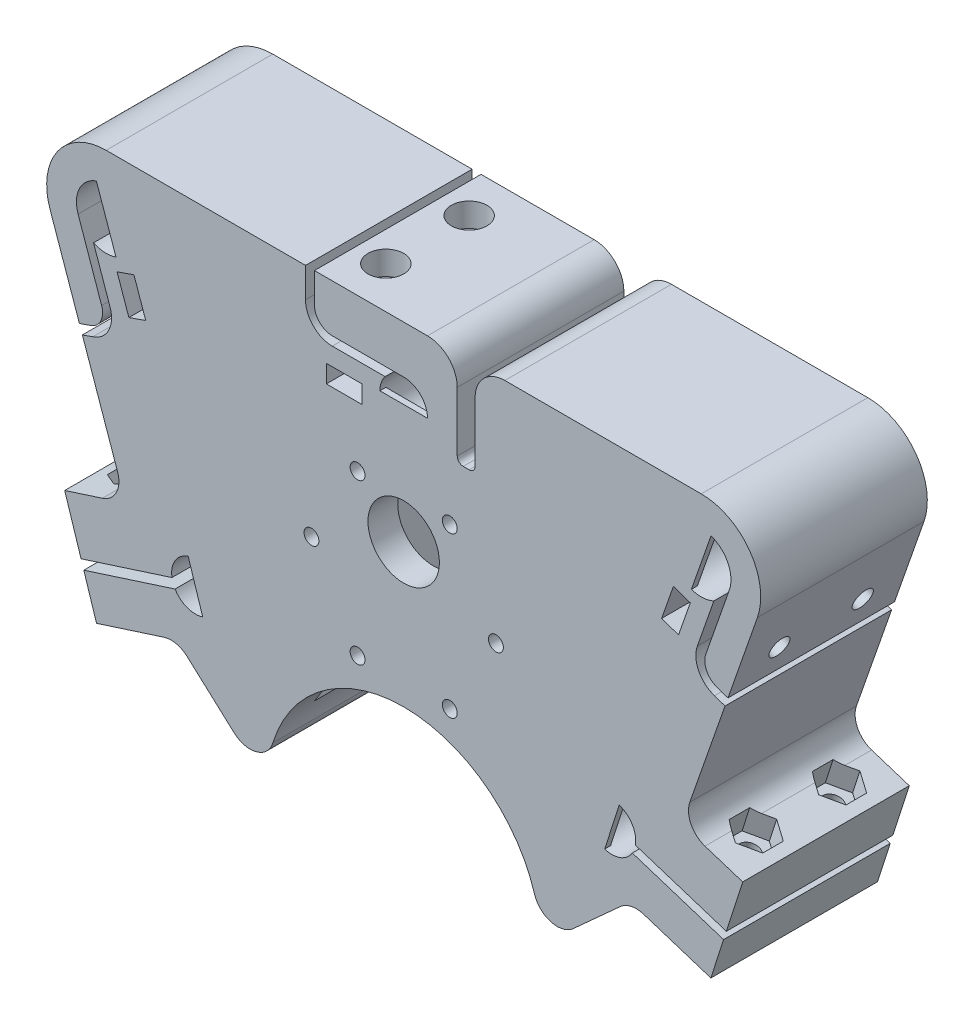
SolidWorks part; units mm, degrees
other "Uwaga1"
sketch "Szkic11" plane through (60, 10, 0) normal (0.4049, 0.0419, -0.9134) x (0.8662, -0.3375, 0.3685)
other "Uwaga2"
sketch "Szkic12" plane through (60, 10, 0) normal (0.4049, 0.0419, -0.9134) x (0.8662, -0.3375, 0.3685)
other "Uwaga3"
sketch "Szkic13"
ref_plane "Płaszczyzna przednia" through (0, 0, 0) normal (0, 0, 1) x (1, 0, 0)
ref_plane "Płaszczyzna górna" through (0, 0, 0) normal (0, 1, 0) x (1, 0, 0)
ref_plane "Płaszczyzna prawa" through (0, 0, 0) normal (1, 0, 0) x (0, 0, -1)
sketch "Szkic1" plane through (0, 0, 0) normal (0, 0, 1) x (1, 0, 0)
  line L0 (-50, 10) -> (4, 10)
  line L1 (-59.4412, -3.296) -> (-43.4971, -48.9664)
  line L2 (43.4971, -48.9664) -> (59.4412, -3.296)
  line L3 (-41.0394, -52.6727) -> (-23, -69)
  line L4 (23, -69) -> (41.0394, -52.6727)
  line L5 (38.4257, -48.0651) -> (43.2433, -49.6122)
  line L6 (38.9457, -46.6566) -> (43.7633, -48.2037)
  line L7 (0, -34.7604) -> (35, -46) construction
  line L8 (38.1168, -55.318) -> (51.621, -59.6546)
  line L9 (51.621, -59.6546) -> (53.7613, -52.9898)
  line L10 (53.7613, -52.9898) -> (43.2433, -49.6122)
  line L11 (43.7633, -48.2037) -> (54.2199, -51.5616)
  line L12 (54.2199, -51.5616) -> (56.9717, -42.9926)
  line L13 (56.9717, -42.9926) -> (46.7307, -39.704)
  line L14 (0, -29) -> (0, -114.3862) construction
  line L15 (0, 2) -> (-12, 2)
  line L16 (-3.1225, 0.5) -> (-12, 0.5)
  line L17 (-16.5, 5) -> (-16.5, 10)
  line L18 (-15, 5) -> (-15, 10)
  line L19 (9, 5) -> (9, -5)
  line L20 (10, -6) -> (11, -6)
  line L21 (12, -5) -> (12, 5)
  line L22 (17, 10) -> (50, 10)
  line L23 (-56.9717, -42.9926) -> (-46.7307, -39.704)
  line L24 (-54.2199, -51.5616) -> (-56.9717, -42.9926)
  line L25 (-43.7633, -48.2037) -> (-54.2199, -51.5616)
  line L26 (-38.9457, -46.6566) -> (-43.7633, -48.2037)
  line L27 (-38.4257, -48.0651) -> (-43.2433, -49.6122)
  line L28 (-53.7613, -52.9898) -> (-43.2433, -49.6122)
  line L29 (-51.621, -59.6546) -> (-53.7613, -52.9898)
  line L30 (-38.1168, -55.318) -> (-51.621, -59.6546)
  line L31 (-54.7206, -1.648) -> (-50.7653, -12.9775)
  line L32 (-52.1248, -4.5261) -> (-49.3471, -12.4823)
  line L33 (-52.6089, -16.7986) -> (-54.4971, -17.4578)
  line L34 (-52.2456, -18.2606) -> (-54.0027, -18.874)
  line L35 (54.7206, -1.648) -> (50.7653, -12.9775)
  line L36 (52.1248, -4.5261) -> (49.3471, -12.4823)
  line L37 (52.6089, -16.7986) -> (54.4971, -17.4578)
  line L38 (52.2456, -18.2606) -> (54.0027, -18.874)
  circle A0 centre (-50, 0) radius 5
  circle A1 centre (50, 0) radius 5
  circle A2 centre (-50, 0) radius 10
  circle A3 centre (50, 0) radius 10
  circle A4 centre (0, -2) radius 4
  circle A5 centre (0, -29) radius 15.5 construction
  circle A6 centre (0, -22) radius 6
  circle A7 centre (15.5, -29) radius 1.25
  circle A8 centre (7.75, -42.4234) radius 1.25
  circle A9 centre (-7.75, -42.4234) radius 1.25
  circle A10 centre (-15.5, -29) radius 1.25
  circle A11 centre (-7.75, -15.5766) radius 1.25
  circle A12 centre (7.75, -15.5766) radius 1.25
  circle A13 centre (-35, -46) radius 4
  circle A14 centre (35, -46) radius 4
  circle A15 centre (-35, -46) radius 9
  circle A16 centre (35, -46) radius 9
  arc A17 (23, -69) -> (-23, -69) centre (0, -69) ccw
  arc A19 (-12, 2) -> (-15, 5) centre (-12, 5) cw
  arc A20 (-12, 0.5) -> (-16.5, 5) centre (-12, 5) cw
  arc A21 (9, 5) -> (4, 10) centre (4, 5) ccw
  arc A22 (12, 5) -> (17, 10) centre (17, 5) cw
  arc A23 (11, -6) -> (12, -5) centre (11, -5) ccw
  arc A24 (9, -5) -> (10, -6) centre (10, -5) ccw
  arc A25 (-50.7653, -12.9775) -> (-52.6089, -16.7986) centre (-53.5977, -13.9663) cw
  arc A26 (-49.3471, -12.4823) -> (-52.2456, -18.2606) centre (-53.5977, -13.9663) cw
  arc A27 (49.3471, -12.4823) -> (52.2456, -18.2606) centre (53.5977, -13.9663) ccw
  arc A28 (50.7653, -12.9775) -> (52.6089, -16.7986) centre (53.5977, -13.9663) ccw
  point P32 (0, -29)
  point P78 (10.1421, 10)
  point P84 (10.1421, -2)
  point P87 (7.1421, -2)
  point P103 (-49.7765, -15.8098)
  dimension "D1" = 10
  dimension "D6" = 8
  dimension "D8" = 31
  dimension "D9" = 12
  dimension "D12" = 2.5
  dimension "D14" = 70
  dimension "D18" = 46
  dimension "D27" = 3
  dimension "D28" = 4.5
  dimension "D31" = 5
  dimension "D32" = 5
  dimension "D33" = 1
  dimension "D38" = 3
  dimension "D2" = 100
  dimension "D3" = 50
  dimension "D7" = 39
  dimension "D10" = 7
  dimension "D11" = 12
  dimension "D15" = 35
  dimension "D16" = 46
  dimension "D19" = 40
  dimension "D20" = 1.5
  dimension "D21" = 7
  dimension "D22" = 20
  dimension "D23" = 9
  dimension "D24" = 1.5
  dimension "D25" = 1.5
  dimension "D26" = 15
  dimension "D29" = 3
  dimension "D30" = 16
  dimension "D34" = 9
  dimension "D35" = 15
  dimension "D36" = 1.5021
  dimension "D37" = 1.5
  dimension "D4" = 5
  dimension "D5" = 5
  dimension "D17" = 5
  dimension "D13" = 6
extrude "Dodanie-wyciągnięcie1" add sketch "Szkic1" along normal blind 28 contours A2 A0 | A17 L4 A16 L2 A3 L0 A2 L1 A15 L3 A12 A11 A10 A9 A8 A7 A6 A4 | A3 A1 | A16 A14 | A15 A13 | A16 L4 L8 L9 L10 | L12 L13 L2 L11 | A15 L28 L29 L30 L3 | L25 L1 L23 L24 | A25 L31 A2 L1 L33 | L35 A28 L37 L2 A3 region at (-33.25, 8.6619, 0) region at (-43.1289, 6.8711, 0) region at (-54.1165, -12.2056, 0) region at (-50.4165, -45.6303, 0) region at (-36.0734, -37.3207, 0) region at (-46.741, -54.5771, 0) region at (56.8711, 6.8711, 0) region at (46.741, -54.5771, 0) region at (54.1165, -12.2056, 0) region at (27.0061, -42.4532, 0) region at (50.4165, -45.6303, 0)
fillet "Zaokrąglenie1" radius 4 6 edges at (-46.7307, -39.704, 14) (-38.1168, -55.318, 14) (-23, -69, 14) (23, -69, 14) (38.1168, -55.318, 14) (46.7307, -39.704, 14)
sketch "Szkic2" plane through (12.5403, -39.0504, 0) normal (0.3058, -0.9521, 0) x (0.9521, 0.3058, 0)
  line L0 (-55.5122, 28) -> (-67.3885, 28) construction
  line L1 (-67.3885, 28) -> (-67.3885, 0) construction
  circle A0 centre (-62.3885, 21) radius 1.7
  circle A1 centre (-62.3885, 7) radius 1.7
  dimension "D1" = 14
  dimension "D4" = 3.4
  dimension "D2" = 7
  dimension "D3" = 5
extrude "Wytnij-wyciągnięcie1" cut sketch "Szkic2" against normal through all
sketch "Szkic3" plane through (12.5403, -39.0504, 0) normal (0.3058, -0.9521, 0) x (0.9521, 0.3058, 0)
  circle A0 centre (-62.3885, 21) radius 3
  circle A1 centre (-62.3885, 7) radius 3
  dimension "D1" = 6
extrude "Wytnij-wyciągnięcie2" cut sketch "Szkic3" against normal blind 3
sketch "Szkic4" plane through (7.1896, -22.3885, 0) normal (-0.3058, 0.9521, 0) x (0.9521, 0.3058, 0)
  line L1 (-62.3885, -24.4641) -> (-59.3885, -22.7321)
  line L2 (-59.3885, -22.7321) -> (-59.3885, -19.2679)
  line L3 (-59.3885, -19.2679) -> (-62.3885, -17.5359)
  line L4 (-62.3885, -17.5359) -> (-65.3885, -19.2679)
  line L5 (-65.3885, -19.2679) -> (-65.3885, -22.7321)
  line L6 (-65.3885, -22.7321) -> (-62.3885, -24.4641)
  line L7 (-62.3885, -10.4641) -> (-59.3885, -8.7321)
  line L8 (-59.3885, -8.7321) -> (-59.3885, -5.2679)
  line L9 (-59.3885, -5.2679) -> (-62.3885, -3.5359)
  line L10 (-62.3885, -3.5359) -> (-65.3885, -5.2679)
  line L11 (-65.3885, -5.2679) -> (-65.3885, -8.7321)
  line L12 (-65.3885, -8.7321) -> (-62.3885, -10.4641)
  circle A0 centre (-62.3885, -21) radius 3 construction
  circle A1 centre (-62.3885, -7) radius 3 construction
  dimension "D1" = 6
extrude "Wytnij-wyciągnięcie3" cut sketch "Szkic4" against normal blind 4 and the other way blind 4
sketch "Szkic5" plane through (-54.0092, -18.8553, 0) normal (-0.9441, -0.3296, 0) x (0, 0, 1)
  line L0 (28, 16.4802) -> (28, 1.4802) construction
  line L1 (28, 1.4802) -> (0, 1.4802) construction
  circle A0 centre (21, 6.4802) radius 1.7
  circle A1 centre (7, 6.4802) radius 1.7
  dimension "D1" = 14
  dimension "D2" = 3.4
  dimension "D3" = 7
  dimension "D4" = 5
extrude "Wytnij-wyciągnięcie4" cut sketch "Szkic5" against normal blind 10
sketch "Szkic6" plane through (-54.0092, -18.8553, 0) normal (-0.9441, -0.3296, 0) x (0, 0, 1)
  line L0 (22.7321, 9.4802) -> (28, 9.4802)
  line L1 (24.4641, 6.4802) -> (22.7321, 9.4802)
  line L2 (22.7321, 9.4802) -> (19.2679, 9.4802)
  line L3 (19.2679, 9.4802) -> (17.5359, 6.4802)
  line L4 (17.5359, 6.4802) -> (19.2679, 3.4802)
  line L5 (19.2679, 3.4802) -> (22.7321, 3.4802)
  line L6 (22.7321, 3.4802) -> (24.4641, 6.4802)
  line L7 (10.4641, 6.4802) -> (8.7321, 9.4802)
  line L8 (8.7321, 9.4802) -> (5.2679, 9.4802)
  line L9 (5.2679, 9.4802) -> (3.5359, 6.4802)
  line L10 (3.5359, 6.4802) -> (5.2679, 3.4802)
  line L11 (5.2679, 3.4802) -> (8.7321, 3.4802)
  line L12 (8.7321, 3.4802) -> (10.4641, 6.4802)
  line L13 (28, 16.4802) -> (28, 1.4802) construction
  line L14 (28, 9.4802) -> (28, 3.4802)
  line L15 (28, 3.4802) -> (22.7321, 3.4802)
  line L16 (5.2679, 9.4802) -> (0, 9.4802)
  line L17 (0, 16.4802) -> (0, 1.4802) construction
  line L18 (0, 9.4802) -> (0, 3.4802)
  line L19 (0, 3.4802) -> (5.2679, 3.4802)
  circle A0 centre (21, 6.4802) radius 3 construction
  circle A1 centre (7, 6.4802) radius 3 construction
  circle M2 centre (21, 6.4802) radius 1.7
  circle M3 centre (7, 6.4802) radius 1.7
  line M4 (0, 16.4802) -> (0, 1.4802)
  line M6 (28, 1.4802) -> (28, 16.4802)
  dimension "D1" = 6
extrude "Wytnij-wyciągnięcie5" cut sketch "Szkic6" against normal blind 3 from offset 9.5 contours L5 L6 L1 L2 L3 L4 M2 | L15 L0 L1 L6 M6 | L19 L10 L9 L16 M4 | L11 L12 L7 L8 L9 L10 M3 | M2 | M3 region at (-56.1452, -12.7372, 25.7706) region at (-56.6245, -11.3643, 23.5187) region at (-55.6658, -14.1101, 9.5187) region at (-56.1452, -12.7372, 2.2294) region at (-56.1452, -12.7372, 21) region at (-56.1452, -12.7372, 7) offset against normal yes
mirror "Lustro1" about plane through (0, 0, 0) normal (1, 0, 0) of "Wytnij-wyciągnięcie5", "Wytnij-wyciągnięcie4", "Wytnij-wyciągnięcie2", "Wytnij-wyciągnięcie1", "Wytnij-wyciągnięcie3"
sketch "Szkic7" plane through (0, 10, 0) normal (0, 1, 0) x (1, 0, 0)
  line L0 (-15, 0) -> (4, 0) construction
  line L1 (-15, -28) -> (-15, 0) construction
  circle A0 centre (-10, -21) radius 1.7
  circle A1 centre (-10, -7) radius 1.7
  dimension "D1" = 3.4
  dimension "D2" = 14
  dimension "D3" = 7
  dimension "D4" = 5
extrude "Wytnij-wyciągnięcie6" cut sketch "Szkic7" against normal blind 14
sketch "Szkic8" plane through (0, 10, 0) normal (0, 1, 0) x (1, 0, 0)
  line L0 (-7, -22.7321) -> (-7, -28)
  line L1 (-10, -24.4641) -> (-7, -22.7321)
  line L2 (-7, -22.7321) -> (-7, -19.2679)
  line L3 (-7, -19.2679) -> (-10, -17.5359)
  line L4 (-10, -17.5359) -> (-13, -19.2679)
  line L5 (-13, -19.2679) -> (-13, -22.7321)
  line L6 (-13, -22.7321) -> (-10, -24.4641)
  line L7 (-10, -10.4641) -> (-7, -8.7321)
  line L8 (-7, -8.7321) -> (-7, -5.2679)
  line L9 (-7, -5.2679) -> (-10, -3.5359)
  line L10 (-10, -3.5359) -> (-13, -5.2679)
  line L11 (-13, -5.2679) -> (-13, -8.7321)
  line L12 (-13, -8.7321) -> (-10, -10.4641)
  line L13 (-15, -28) -> (4, -28) construction
  line L14 (-7, -28) -> (-13, -28)
  line L15 (-13, -28) -> (-13, -22.7321)
  line L16 (-7, -5.2679) -> (-7, 0)
  line L17 (-15, 0) -> (4, 0) construction
  line L18 (-7, 0) -> (-13, 0)
  line L19 (-13, 0) -> (-13, -5.2679)
  circle A0 centre (-10, -21) radius 3 construction
  circle A1 centre (-10, -7) radius 3 construction
  circle M1 centre (-10, -21) radius 1.7
  circle M2 centre (-10, -7) radius 1.7
  line M3 (4, 0) -> (-15, 0)
  line M5 (-15, -28) -> (4, -28)
  dimension "D1" = 6
extrude "Wytnij-wyciągnięcie7" cut sketch "Szkic8" against normal blind 3 from offset 12.5 contours L5 L6 L1 L2 L3 L4 M1 | M1 | L15 L0 L1 L6 M5 | M2 | L11 L12 L7 L8 L9 L10 M2 | L19 L10 L9 L16 M3 region at (-10, 10, 25.7706) region at (-8.5458, 10, 23.5187) region at (-11.4542, 10, 9.5187) region at (-10, 10, 2.2294) region at (-10, 10, 21) region at (-10, 10, 7) offset against normal yes
sketch "Szkic9" plane through (0, 0, 28) normal (0, 0, 1) x (1, 0, 0)
  line L0 (-36.223, -42.1916) -> (-33.777, -49.8084)
  line L1 (36.223, -42.1916) -> (33.777, -49.8084)
  line L2 (-51.648, 4.7206) -> (-48.352, -4.7206)
  line L3 (51.648, 4.7206) -> (48.352, -4.7206)
  line L4 (-4, -2) -> (4, -2)
  line L36 (-36.4063, -56.8662) -> (-28.4915, -64.0297)
  line L37 (28.4915, -64.0297) -> (36.4063, -56.8662)
  line L38 (40.3135, -56.0234) -> (51.621, -59.6546)
  line L39 (51.621, -59.6546) -> (53.7613, -52.9898)
  line L40 (53.7613, -52.9898) -> (38.4257, -48.0651)
  line L41 (38.9457, -46.6566) -> (54.2199, -51.5616)
  line L42 (54.2199, -51.5616) -> (56.9717, -42.9926)
  line L43 (56.9717, -42.9926) -> (50.6362, -40.9581)
  line L44 (48.0827, -35.8313) -> (54.0027, -18.874)
  line L45 (54.0027, -18.874) -> (52.2456, -18.2606)
  line L46 (49.3471, -12.4823) -> (52.1248, -4.5261)
  line L47 (54.7206, -1.648) -> (50.7653, -12.9775)
  line L48 (52.6089, -16.7986) -> (54.4971, -17.4578)
  line L49 (54.4971, -17.4578) -> (59.4412, -3.296)
  line L50 (50, 10) -> (17, 10)
  line L51 (12, 5) -> (12, -5)
  line L52 (11, -6) -> (10, -6)
  line L53 (9, -5) -> (9, 5)
  line L54 (4, 10) -> (-15, 10)
  line L55 (-15, 10) -> (-15, 5)
  line L56 (-12, 2) -> (0, 2)
  line L57 (-3.1225, 0.5) -> (-12, 0.5)
  line L58 (-16.5, 5) -> (-16.5, 10)
  line L59 (-16.5, 10) -> (-50, 10)
  line L60 (-59.4412, -3.296) -> (-54.4971, -17.4578)
  line L61 (-54.4971, -17.4578) -> (-52.6089, -16.7986)
  line L62 (-50.7653, -12.9775) -> (-54.7206, -1.648)
  line L63 (-52.1248, -4.5261) -> (-49.3471, -12.4823)
  line L64 (-52.2456, -18.2606) -> (-54.0027, -18.874)
  line L65 (-54.0027, -18.874) -> (-48.0827, -35.8313)
  line L66 (-50.6362, -40.9581) -> (-56.9717, -42.9926)
  line L67 (-56.9717, -42.9926) -> (-54.2199, -51.5616)
  line L68 (-54.2199, -51.5616) -> (-38.9457, -46.6566)
  line L69 (-38.4257, -48.0651) -> (-53.7613, -52.9898)
  line L70 (-53.7613, -52.9898) -> (-51.621, -59.6546)
  line L71 (-51.621, -59.6546) -> (-40.3135, -56.0234)
  line L72 (-36.4063, -56.8662) -> (-28.4915, -64.0297)
  line L73 (28.4915, -64.0297) -> (36.4063, -56.8662)
  line L74 (40.3135, -56.0234) -> (51.621, -59.6546)
  line L75 (51.621, -59.6546) -> (53.7613, -52.9898)
  line L76 (53.7613, -52.9898) -> (38.4257, -48.0651)
  line L77 (38.9457, -46.6566) -> (54.2199, -51.5616)
  line L78 (54.2199, -51.5616) -> (56.9717, -42.9926)
  line L79 (56.9717, -42.9926) -> (50.6362, -40.9581)
  line L80 (48.0827, -35.8313) -> (54.0027, -18.874)
  line L81 (54.0027, -18.874) -> (52.2456, -18.2606)
  line L82 (49.3471, -12.4823) -> (52.1248, -4.5261)
  line L83 (54.7206, -1.648) -> (50.7653, -12.9775)
  line L84 (52.6089, -16.7986) -> (54.4971, -17.4578)
  line L85 (54.4971, -17.4578) -> (59.4412, -3.296)
  line L86 (50, 10) -> (17, 10)
  line L87 (12, 5) -> (12, -5)
  line L88 (11, -6) -> (10, -6)
  line L89 (9, -5) -> (9, 5)
  line L90 (4, 10) -> (-15, 10)
  line L91 (-15, 10) -> (-15, 5)
  line L92 (-12, 2) -> (0, 2)
  line L93 (-3.1225, 0.5) -> (-12, 0.5)
  line L94 (-16.5, 5) -> (-16.5, 10)
  line L95 (-16.5, 10) -> (-50, 10)
  line L96 (-59.4412, -3.296) -> (-54.4971, -17.4578)
  line L97 (-54.4971, -17.4578) -> (-52.6089, -16.7986)
  line L98 (-50.7653, -12.9775) -> (-54.7206, -1.648)
  line L99 (-52.1248, -4.5261) -> (-49.3471, -12.4823)
  line L100 (-52.2456, -18.2606) -> (-54.0027, -18.874)
  line L101 (-54.0027, -18.874) -> (-48.0827, -35.8313)
  line L102 (-50.6362, -40.9581) -> (-56.9717, -42.9926)
  line L103 (-56.9717, -42.9926) -> (-54.2199, -51.5616)
  line L104 (-54.2199, -51.5616) -> (-38.9457, -46.6566)
  line L105 (-38.4257, -48.0651) -> (-53.7613, -52.9898)
  line L106 (-53.7613, -52.9898) -> (-51.621, -59.6546)
  line L107 (-51.621, -59.6546) -> (-40.3135, -56.0234)
  arc A24 (-28.4915, -64.0297) -> (-21.984, -62.2397) centre (-25.8074, -61.064) ccw
  arc A25 (21.984, -62.2397) -> (-21.984, -62.2397) centre (0, -69) ccw
  arc A26 (21.984, -62.2397) -> (28.4915, -64.0297) centre (25.8074, -61.064) ccw
  arc A27 (40.3135, -56.0234) -> (36.4063, -56.8662) centre (39.0904, -59.8318) ccw
  arc A28 (38.9457, -46.6566) -> (38.4257, -48.0651) centre (35, -46) ccw
  arc A29 (48.0827, -35.8313) -> (50.6362, -40.9581) centre (51.8592, -37.1497) ccw
  arc A30 (49.3471, -12.4823) -> (52.2456, -18.2606) centre (53.5977, -13.9663) ccw
  arc A31 (54.7206, -1.648) -> (52.1248, -4.5261) centre (50, 0) ccw
  arc A32 (50.7653, -12.9775) -> (52.6089, -16.7986) centre (53.5977, -13.9663) ccw
  arc A33 (59.4412, -3.296) -> (50, 10) centre (50, 0) ccw
  arc A34 (17, 10) -> (12, 5) centre (17, 5) ccw
  arc A35 (11, -6) -> (12, -5) centre (11, -5) ccw
  arc A36 (9, -5) -> (10, -6) centre (10, -5) ccw
  arc A37 (9, 5) -> (4, 10) centre (4, 5) ccw
  arc A38 (-15, 5) -> (-12, 2) centre (-12, 5) ccw
  arc A39 (-3.1225, 0.5) -> (0, 2) centre (0, -2) ccw
  arc A40 (-16.5, 5) -> (-12, 0.5) centre (-12, 5) ccw
  arc A41 (-50, 10) -> (-59.4412, -3.296) centre (-50, 0) ccw
  arc A42 (-52.6089, -16.7986) -> (-50.7653, -12.9775) centre (-53.5977, -13.9663) ccw
  arc A43 (-52.1248, -4.5261) -> (-54.7206, -1.648) centre (-50, 0) ccw
  arc A44 (-52.2456, -18.2606) -> (-49.3471, -12.4823) centre (-53.5977, -13.9663) ccw
  arc A45 (-50.6362, -40.9581) -> (-48.0827, -35.8313) centre (-51.8592, -37.1497) ccw
  arc A46 (-38.4257, -48.0651) -> (-38.9457, -46.6566) centre (-35, -46) ccw
  arc A47 (-36.4063, -56.8662) -> (-40.3135, -56.0234) centre (-39.0904, -59.8318) ccw
  arc A48 (-28.4915, -64.0297) -> (-21.984, -62.2397) centre (-25.8074, -61.064) ccw
  arc A49 (21.984, -62.2397) -> (-21.984, -62.2397) centre (0, -69) ccw
  arc A50 (21.984, -62.2397) -> (28.4915, -64.0297) centre (25.8074, -61.064) ccw
  arc A51 (40.3135, -56.0234) -> (36.4063, -56.8662) centre (39.0904, -59.8318) ccw
  arc A52 (38.9457, -46.6566) -> (38.4257, -48.0651) centre (35, -46) ccw
  arc A53 (48.0827, -35.8313) -> (50.6362, -40.9581) centre (51.8592, -37.1497) ccw
  arc A54 (49.3471, -12.4823) -> (52.2456, -18.2606) centre (53.5977, -13.9663) ccw
  arc A55 (54.7206, -1.648) -> (52.1248, -4.5261) centre (50, 0) ccw
  arc A56 (50.7653, -12.9775) -> (52.6089, -16.7986) centre (53.5977, -13.9663) ccw
  arc A57 (59.4412, -3.296) -> (50, 10) centre (50, 0) ccw
  arc A58 (17, 10) -> (12, 5) centre (17, 5) ccw
  arc A59 (11, -6) -> (12, -5) centre (11, -5) ccw
  arc A60 (9, -5) -> (10, -6) centre (10, -5) ccw
  arc A61 (9, 5) -> (4, 10) centre (4, 5) ccw
  arc A62 (-15, 5) -> (-12, 2) centre (-12, 5) ccw
  arc A63 (-3.1225, 0.5) -> (0, 2) centre (0, -2) ccw
  arc A64 (-16.5, 5) -> (-12, 0.5) centre (-12, 5) ccw
  arc A65 (-50, 10) -> (-59.4412, -3.296) centre (-50, 0) ccw
  arc A66 (-52.6089, -16.7986) -> (-50.7653, -12.9775) centre (-53.5977, -13.9663) ccw
  arc A67 (-52.1248, -4.5261) -> (-54.7206, -1.648) centre (-50, 0) ccw
  arc A68 (-52.2456, -18.2606) -> (-49.3471, -12.4823) centre (-53.5977, -13.9663) ccw
  arc A69 (-50.6362, -40.9581) -> (-48.0827, -35.8313) centre (-51.8592, -37.1497) ccw
  arc A70 (-38.4257, -48.0651) -> (-38.9457, -46.6566) centre (-35, -46) ccw
  arc A71 (-36.4063, -56.8662) -> (-40.3135, -56.0234) centre (-39.0904, -59.8318) ccw
  dimension "D1" = 0
extrude "Dodanie-wyciągnięcie2" add sketch "Szkic9" against normal blind 1 contours L2 A67 | L4 A63 | L3 A55 | L1 A52 | L0 A70 region at (-33.3836, -45.4809, 28) region at (-47.9965, 0.6994, 28) region at (33.3836, -45.4809, 28) region at (0, -3.6977, 28) region at (47.9965, 0.6994, 28)
sketch "Szkic10" plane through (0, 0, 0) normal (0, 0, -1) x (-1, 0, 0)
  line L0 (7.75, -42.4234) -> (-7.75, -15.5766) construction
  line L1 (-7.75, -15.5766) -> (-15.5, -29) construction
  line L2 (-15.5, -29) -> (15.5, -29) construction
  line L3 (20, -29) -> (20, -58.8701)
  line L4 (-20, -29) -> (-20, -58.8701)
  line L5 (-20, -58.8701) -> (20, -58.8701)
  circle A0 centre (-7.75, -15.5766) radius 1.25 construction
  circle A1 centre (7.75, -42.4234) radius 1.25 construction
  circle A2 centre (-15.5, -29) radius 1.25 construction
  circle A3 centre (15.5, -29) radius 1.25 construction
  circle A4 centre (-7.75, -15.5766) radius 1.25 construction
  circle A5 centre (7.75, -42.4234) radius 1.25 construction
  circle A6 centre (-15.5, -29) radius 1.25 construction
  circle A7 centre (15.5, -29) radius 1.25 construction
  circle A8 centre (0, -29) radius 20
  dimension "D1" = 40
extrude "Wytnij-wyciągnięcie8" cut sketch "Szkic10" against normal blind 23 contours A8 L4 L5 L3 | A8 region at (0, -29, 0) region at (0, -51.0855, 0)
sketch "Szkic14" plane through (0, 10, 0) normal (0, 1, 0) x (1, 0, 0)
  circle A0 centre (-10, -7) radius 3
  circle A1 centre (-10, -21) radius 3
  dimension "D1" = 6
extrude "Wytnij-wyciągnięcie9" cut sketch "Szkic14" against normal blind 4
sketch "Szkic15" plane through (44.6861, -49.3721, 0) normal (0.671, -0.7414, 0) x (0.7414, 0.671, 0)
  line L0 (-21.8428, 28) -> (-11.1677, 28) construction
  line L2 (-21.8428, 28) -> (-21.8428, 0) construction
  circle A0 centre (-16.8428, 21) radius 2
  circle A1 centre (-16.8428, 7) radius 2
  point P4 (0, 0)
  point P7 (0, 0)
  point P8 (-16.8494, 21)
  dimension "D1" = 14
  dimension "D3" = 4
  dimension "D2" = 7
  dimension "D4" = 5
extrude "Wytnij-wyciągnięcie10" cut sketch "Szkic15" against normal blind 10
mirror "Lustro2" about plane through (0, 0, 0) normal (1, 0, 0) of "Wytnij-wyciągnięcie10"
